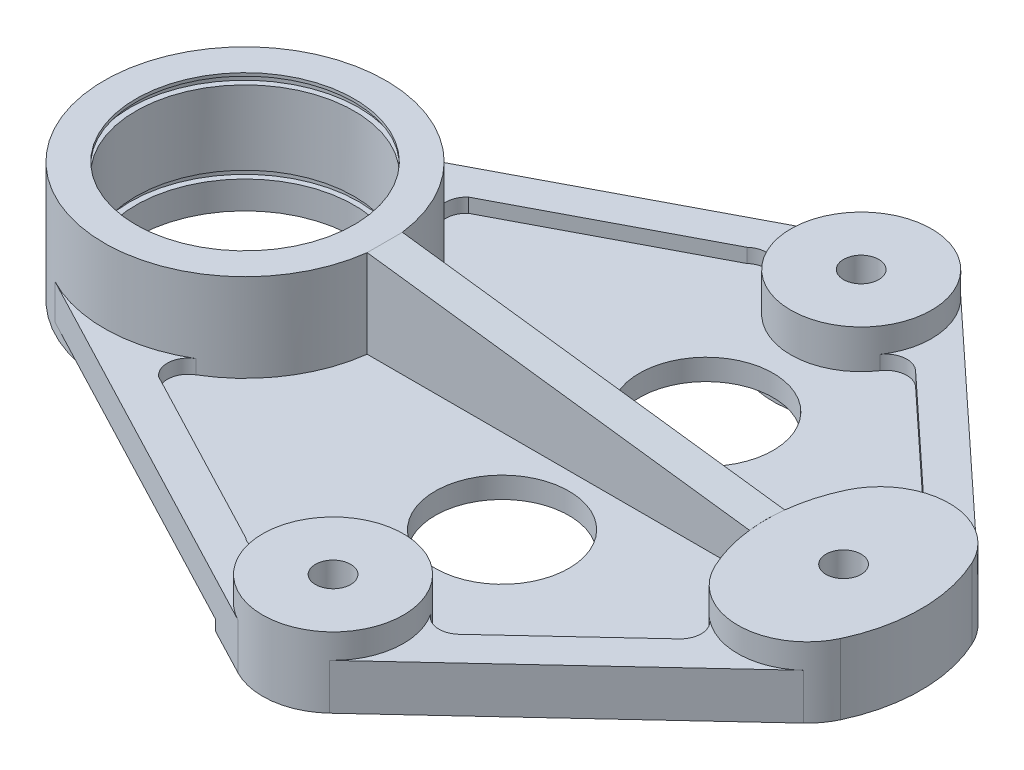
SolidWorks part; units mm, degrees
ref_plane "Front Plane" through (0, 0, 0) normal (0, 0, 1) x (1, 0, 0)
ref_plane "Top Plane" through (0, 0, 0) normal (0, 1, 0) x (1, 0, 0)
ref_plane "Right Plane" through (0, 0, 0) normal (1, 0, 0) x (0, 0, -1)
sketch "Sketch1" plane through (0, 0, 0) normal (0, 1, 0) x (1, 0, 0)
  line L0 (-4.6427, 46.3569) -> (-59.2854, 17.7139)
  line L1 (24.1801, 2.5) -> (-30.1569, 2.5)
  line L2 (6.8096, 44.8232) -> (41.7074, 12.3731)
  line L3 (-30.1569, -2.5) -> (24.1801, -2.5)
  line L4 (0, 77.8679) -> (0, -114.4116) construction
  line L5 (-0.5613, 0) -> (-167.8643, 0) construction
  line L6 (-4.6427, -46.3569) -> (-59.2854, -17.7139)
  line L7 (41.7074, -12.3731) -> (6.8096, -44.8232)
  line L8 (35, 0) -> (35, 10.5297) construction
  line L9 (24, 0) -> (46, 0) construction
  line L10 (-14.3498, 35.6233) -> (-40.3025, 22.0192)
  line L11 (-50, 0) -> (35, 0) construction
  line L12 (29.0537, 17.3117) -> (12.8747, 32.3559)
  line L13 (-14.2411, -35.6803) -> (-40.173, -22.0871)
  line L14 (12.7962, -32.4289) -> (28.9749, -17.3849)
  line L15 (-38.289, 19.7953) -> (-12.3363, 33.3994) construction
  line L16 (-14.3498, 35.6233) -> (-9.8223, 35.6233) construction
  line L17 (-40.3025, 22.0192) -> (-40.3025, 17.4917) construction
  line L18 (26.9484, 15.1744) -> (10.7695, 30.2186) construction
  line L19 (12.8747, 32.3559) -> (8.5754, 32.3559) construction
  line L20 (29.0537, 17.3117) -> (29.0537, 13.0124) construction
  line L21 (10.7688, -30.2176) -> (26.9475, -15.1737) construction
  line L22 (12.7962, -32.4289) -> (9.7469, -35.2643) construction
  line L23 (28.9749, -17.3849) -> (32.0243, -14.5495) construction
  line L24 (-38.2586, -19.7773) -> (-12.3267, -33.3705) construction
  line L25 (-40.173, -22.0871) -> (-45.2474, -19.4271) construction
  line L26 (-14.2411, -35.6803) -> (-9.83, -39.3363) construction
  line L27 (1, 14.5) -> (1, -14.5) construction
  circle A0 centre (-50, 0) radius 20
  circle A1 centre (-50, 0) radius 15.5
  circle A2 centre (0, -37.5) radius 10
  circle A3 centre (0, -37.5) radius 2.5
  circle A4 centre (0, 37.5) radius 2.5
  circle A5 centre (0, 37.5) radius 10
  circle A6 centre (35, 0) radius 2.5
  arc A7 (26.0823, -9.3427) -> (43.9177, -9.3427) centre (35, -5.1597) ccw
  arc A8 (26.0823, 9.3427) -> (43.9177, 9.3427) centre (35, 5.1597) cw
  arc A9 (26.0823, 9.3427) -> (26.0823, -9.3427) centre (46, 0) ccw
  arc A10 (43.9177, 9.3427) -> (43.9177, -9.3427) centre (24, 0) cw
  arc A11 (-40.3025, 22.0192) -> (-39.8165, 17.2133) centre (-38.289, 19.7953) ccw
  arc A12 (-14.3498, 35.6233) -> (-9.4895, 34.3457) centre (-12.3363, 33.3994) cw
  arc A13 (29.0537, 17.3117) -> (28.8282, 12.8364) centre (26.9484, 15.1744) cw
  arc A14 (12.8747, 32.3559) -> (8.2842, 31.8989) centre (10.7695, 30.2186) ccw
  arc A15 (28.9749, -17.3849) -> (28.8275, -12.8358) centre (26.9475, -15.1737) ccw
  arc A16 (12.7962, -32.4289) -> (8.2837, -31.8982) centre (10.7688, -30.2176) cw
  arc A17 (-40.173, -22.0871) -> (-39.7901, -17.1976) centre (-38.2586, -19.7773) cw
  arc A18 (-14.2411, -35.6803) -> (-9.4821, -34.3235) centre (-12.3267, -33.3705) ccw
  circle A19 centre (1, -14.5) radius 9.5
  circle A20 centre (1, 14.5) radius 9.5
  dimension "D1" = 40
  dimension "D2" = 5
  dimension "35" = 31
  dimension "D6" = 20
  dimension "D7" = 5
  dimension "D8" = 9.85
  dimension "D9" = 5
  dimension "D13" = 5
  dimension "D4" = 20
  dimension "D5" = 22
  dimension "D17" = 3
  dimension "D18" = 3
  dimension "D19" = 3
  dimension "D20" = 3
  dimension "D21" = 19
  dimension "D3" = 75
  dimension "D10" = 5
  dimension "D11" = 50
  dimension "D12" = 35
  dimension "D14" = 5
  dimension "D15" = 5
  dimension "D16" = 5
  dimension "D22" = 29
  dimension "D23" = 1
extrude "Boss-Extrude1" add sketch "Sketch1" along normal blind 3 contours L13 A18 A2 A16 L14 A15 A7 A9 L3 A0 A17 A19 | L12 A14 A5 A12 L10 A11 A0 L1 A9 A8 A13 A20 region at (-1.4713, 0, -26.8119) region at (-32.6133, 0, 11.3958)
extrude "Boss-Extrude2" add sketch "Sketch1<3>" along normal blind 5 contours A18 L13 A17 A0 L6 A2 | L14 A16 A2 L7 A7 A15 | A14 L12 A13 A8 L2 A5 | L10 A12 A5 L0 A0 A11 region at (-29.7837, 0, -30.3455) region at (22.5889, 0, -26.7708) region at (-29.781, 0, 30.3426) region at (22.5888, 0, 26.7707)
sketch "Sketch1<3>" plane through (0, 0, 0) normal (0, 1, 0) x (1, 0, 0) same geometry as "Sketch1"
extrude "Boss-Extrude3" add sketch "Sketch1<4>" along normal blind 15.5 and the other way blind 1.5 contours A9 L1 A0 L3 region at (-3.0024, 0, 0)
sketch "Sketch1<4>" plane through (0, 0, 0) normal (0, 1, 0) x (1, 0, 0) same geometry as "Sketch1"
extrude "Boss-Extrude4" add sketch "Sketch1<5>" along normal blind 8.5 and the other way blind 1.5 contours A2 A3 | A5 A4 region at (1.2898, 0, -47.1312) region at (-9.0154, 0, 41.1256)
sketch "Sketch1<5>" plane through (0, 0, 0) normal (0, 1, 0) x (1, 0, 0) same geometry as "Sketch1"
extrude "Boss-Extrude5" add sketch "Sketch1<6>" along normal blind 8.5 and the other way blind 1.5 contours A10 A8 A9 A7 A6 region at (42.6574, 0, -10.7447)
sketch "Sketch1<6>" plane through (0, 0, 0) normal (0, 1, 0) x (1, 0, 0) same geometry as "Sketch1"
extrude "Boss-Extrude6" add sketch "Sketch1<7>" along normal blind 15.5 and the other way blind 1.5 contours A0 A1 region at (-49.5005, 0, -19.4279)
sketch "Sketch1<7>" plane through (0, 0, 0) normal (0, 1, 0) x (1, 0, 0) same geometry as "Sketch1"
sketch "Sketch3" plane through (0, 0, 2.5) normal (0, 0, 1) x (1, 0, 0)
  line L0 (-30.1569, 15.5) -> (24.1425, 8.5)
  line L1 (24.1425, 8.5) -> (24.1425, 15.5)
  line L2 (24.1425, 15.5) -> (-30.1569, 15.5)
extrude "Cut-Extrude1" cut sketch "Sketch3" against normal up to next
sketch "Sketch8" plane through (0, 0, 0) normal (0, 0, 1) x (1, 0, 0)
  line L0 (-4.6427, 0) -> (-59.2854, 0) construction
  line L1 (-33.8284, 15.075) -> (-50.0784, 15.075)
  line L2 (-33.8284, 15.075) -> (-33.8284, 14)
  line L3 (-33.8284, 14) -> (-50.0784, 14)
  line L4 (-50.0784, 15.075) -> (-50.0784, 14)
  line L5 (-33.8284, 3.5) -> (-50.0784, 3.5)
  line L6 (-33.8284, 3.5) -> (-33.8284, 2.425)
  line L7 (-33.8284, 2.425) -> (-50.0784, 2.425)
  line L8 (-50.0784, 3.5) -> (-50.0784, 2.425)
  line L10 (-70, 15.5) -> (-70, -1.5) construction
  line L11 (-70, 2.9625) -> (-50.0784, 2.9625) construction
  line L12 (-33.8284, 5) -> (-30.1569, 5) construction
  line L13 (-4.6427, 5) -> (-59.2854, 5) construction
  line L14 (-30.1569, 3) -> (-30.1569, 15.5) construction
  line L16 (-33.8284, 14.5375) -> (-30.1569, 14.5375) construction
  line L17 (-50.0784, -1.5) -> (-50.0784, 18.5708) construction
  line L18 (-50.0784, -1.5) -> (-70, -1.5) construction
  line L19 (-50.0784, -1.5) -> (-30.1569, -1.5) construction
  dimension "D1" = 1.075
  dimension "D2" = 1.075
  dimension "D3" = 16.25
  dimension "D4" = 16.25
  dimension "D5" = 3.5
  dimension "D6" = 10.5
revolve "Cut-Revolve2" cut sketch "Sketch8" angle 360 about L4
sketch "Sketch11" plane through (0, 0, 0) normal (0, -1, 0) x (1, 0, 0)
  line L0 (6.8096, -44.8232) -> (41.7074, -12.3731) construction
  line L1 (41.7074, 12.3731) -> (6.8096, 44.8232) construction
  line L2 (6.8096, -44.8232) -> (41.7074, -12.3731)
  line L3 (41.7074, 12.3731) -> (6.8096, 44.8232)
  line L4 (0, 0) -> (43.3585, 0) construction
  line L5 (21.5, 11.4217) -> (21.5, 2.5)
  line L6 (20.5429, 13.6187) -> (7.9213, 25.3549)
  line L8 (-4.6427, 46.3569) -> (-59.2854, 17.7139) construction
  line L9 (-30.1569, 2.5) -> (24.1425, 2.5) construction
  line L10 (20.5429, -13.6187) -> (7.9213, -25.3549)
  line L11 (21.5, -11.4217) -> (21.5, -2.5)
  line L12 (21.5, 2.5) -> (24.1425, 2.5)
  line L13 (21.5, -2.5) -> (24.1425, -2.5)
  line L14 (-11.2854, 42.8749) -> (-4.6427, 46.3569)
  line L15 (-11.2854, -42.8749) -> (-4.6427, -46.3569)
  arc A0 (26.0823, -9.3427) -> (43.9177, -9.3427) centre (35, -5.1597) ccw construction
  arc A1 (24.1425, -2.5) -> (26.0823, -9.3427) centre (46, 0) ccw construction
  arc A2 (43.9177, 9.3427) -> (26.0823, 9.3427) centre (35, 5.1597) ccw construction
  arc A3 (26.0823, 9.3427) -> (24.1425, 2.5) centre (46, 0) ccw construction
  arc A4 (6.8096, -44.8232) -> (-4.6427, -46.3569) centre (0, -37.5) ccw construction
  circle A5 centre (0, 37.5) radius 10 construction
  arc A6 (26.0823, -9.3427) -> (41.7074, -12.3731) centre (35, -5.1597) ccw
  arc A7 (24.1425, -2.5) -> (26.0823, -9.3427) centre (46, 0) ccw
  arc A8 (41.7074, 12.3731) -> (26.0823, 9.3427) centre (35, 5.1597) ccw
  arc A9 (26.0823, 9.3427) -> (24.1425, 2.5) centre (46, 0) ccw
  arc A10 (6.8096, -44.8232) -> (-4.6427, -46.3569) centre (0, -37.5) ccw
  arc A11 (-4.6427, 46.3569) -> (6.8096, 44.8232) centre (0, 37.5) ccw
  arc A12 (21.5, 11.4217) -> (20.5429, 13.6187) centre (18.5, 11.4217) ccw
  arc A13 (4.7407, 25.9339) -> (-11.2854, 42.8749) centre (0, 37.5) cw
  arc A14 (7.9213, 25.3549) -> (4.7407, 25.9339) centre (5.8785, 23.158) ccw
  arc A15 (4.7407, -25.9339) -> (-11.2854, -42.8749) centre (0, -37.5) ccw
  arc A16 (7.9213, -25.3549) -> (4.7407, -25.9339) centre (5.8785, -23.158) cw
  arc A17 (21.5, -11.4217) -> (20.5429, -13.6187) centre (18.5, -11.4217) cw
  point P2 (42.1591, 11.9251)
  point P7 (-5.2032, 46.0631)
  point P32 (42.1583, -11.9258)
  point P38 (-4.6427, 46.3569)
  dimension "D1" = 12.5
  dimension "D2" = 3
  dimension "D5" = 3
  dimension "D3" = 13.5
  dimension "D4" = 13.5
extrude "Boss-Extrude7" add sketch "Sketch11" along normal blind 1.5
